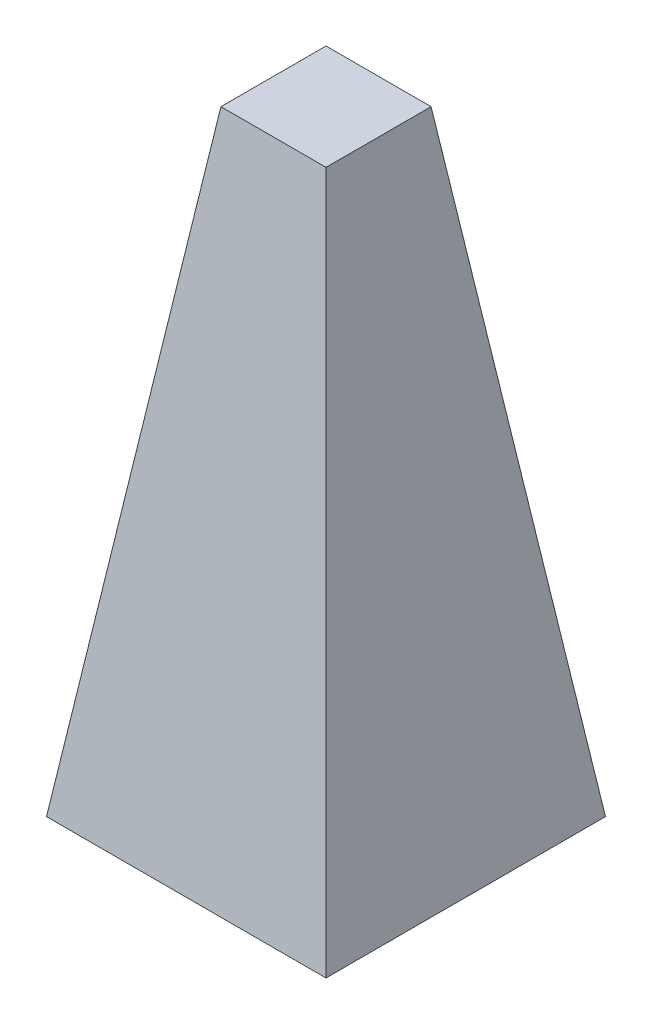
SolidWorks part; units mm, degrees
ref_plane "Front Plane" through (0, 0, 0) normal (0, 0, 1) x (1, 0, 0)
ref_plane "Top Plane" through (0, 0, 0) normal (0, 1, 0) x (1, 0, 0)
ref_plane "Right Plane" through (0, 0, 0) normal (1, 0, 0) x (0, 0, -1)
sketch "Sketch1" plane through (0, 0, 0) normal (0, 1, 0) x (1, 0, 0)
  line L1 (-63.5, -63.5) -> (63.5, -63.5)
  line L2 (-63.5, -63.5) -> (-63.5, 63.5)
  line L3 (-63.5, 63.5) -> (63.5, 63.5)
  line L4 (63.5, -63.5) -> (63.5, 63.5)
  line L5 (-63.5, -63.5) -> (63.5, 63.5) construction
  line L6 (-63.5, 63.5) -> (63.5, -63.5) construction
  point P0 (0, 0)
  dimension "D1" = 127
ref_plane "Plane1" through (0, 279.4, 0) normal (0, 1, 0) x (1, 0, 0)
sketch "Sketch2" plane through (0, 279.4, 0) normal (0, 1, 0) x (1, 0, 0)
  line L1 (-23.876, -23.876) -> (23.876, -23.876)
  line L2 (-23.876, -23.876) -> (-23.876, 23.876)
  line L3 (-23.876, 23.876) -> (23.876, 23.876)
  line L4 (23.876, -23.876) -> (23.876, 23.876)
  line L5 (-23.876, -23.876) -> (23.876, 23.876) construction
  line L6 (-23.876, 23.876) -> (23.876, -23.876) construction
  point P0 (0, 0)
  dimension "D1" = 47.752
loft "Loft1" add profiles "Sketch1", "Sketch2" connector at (63.5, 0, -63.5) connector at (23.876, 279.4, -23.876)
